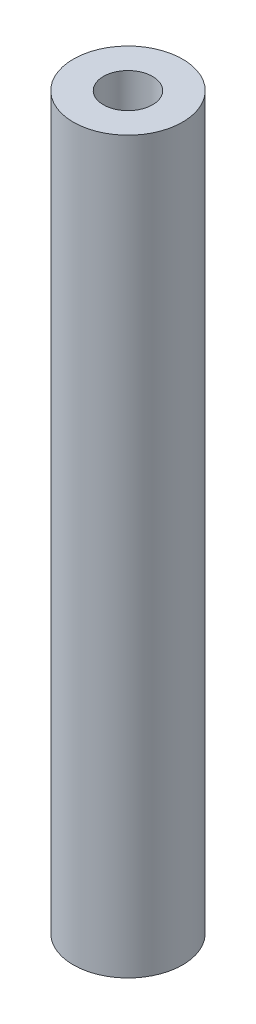
SolidWorks part; units mm, degrees
ref_plane "Front Plane" through (0, 0, 0) normal (0, 0, 1) x (1, 0, 0)
ref_plane "Top Plane" through (0, 0, 0) normal (0, 1, 0) x (1, 0, 0)
ref_plane "Right Plane" through (0, 0, 0) normal (1, 0, 0) x (0, 0, -1)
sketch "Szkic1" plane through (0, 0, 0) normal (0, 1, 0) x (1, 0, 0)
  circle A0 centre (-3.4437, 0) radius 2.25
  circle A1 centre (-3.4437, 0) radius 5
  dimension "D1" = 4.5
  dimension "D2" = 10
extrude "Dodanie-wyciągnięcie1" add sketch "Szkic1" along normal blind 66.8
